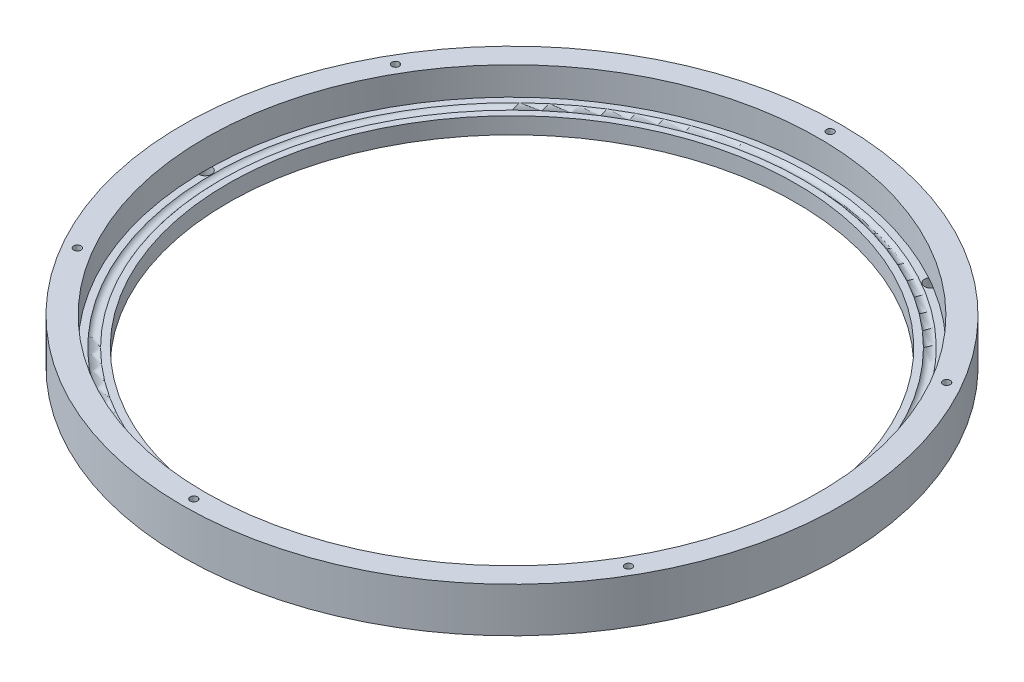
SolidWorks part; units mm, degrees
ref_plane "Front Plane" through (0, 0, 0) normal (0, 0, 1) x (1, 0, 0)
ref_plane "Top Plane" through (0, 0, 0) normal (0, 1, 0) x (1, 0, 0)
ref_plane "Right Plane" through (0, 0, 0) normal (1, 0, 0) x (0, 0, -1)
sketch "Sketch1" plane through (0, 0, 0) normal (0, 1, 0) x (1, 0, 0)
  line L0 (47.1487, -81.664) -> (0, 0) construction
  line L1 (0, 0) -> (0, -32.7983) construction
  circle A0 centre (0, 0) radius 87.3125
  circle A1 centre (0, 0) radius 101.2825
  circle A3 centre (0, 0) radius 94.2975
  circle A4 centre (0, -97.79) radius 1.1303
  circle A5 centre (47.1487, -81.664) radius 1.9939
  circle A6 centre (47.1487, -81.664) radius 5.588
  dimension "D1" = 174.625
  dimension "D5" = 2.2606
  dimension "D7" = 3.9878
  dimension "D9" = 11.176
  dimension "D4" = 97.79
  dimension "D6" = 94.2975
  dimension "D8" = 30
  dimension "D2" = 13.97
  dimension "D3" = 6.985
extrude "Boss-Extrude1" add sketch "Sketch1" along normal blind 5.08 contours A3 A0 | A1 A4 A3 | A3 A6 A5 | A3 A6 A5 region at (-98.4178, 0, 0) region at (80.6769, 0, 43.4438) region at (45.8339, 0, 79.3867) region at (48.4279, 0, 83.8795)
extrude "Boss-Extrude3" add sketch "Sketch1<3>" along normal blind 8.636 from surface contours A1 A4 A3 | A3 A5 | A3 A6 A5 region at (-98.4178, 0, 0) region at (48.4279, 0, 83.8795) region at (47.57, 0, 82.3936) starting at face at (47.1487, 5.08, 83.6579)
sketch "Sketch1<3>" plane through (0, 0, 0) normal (0, 1, 0) x (1, 0, 0) same geometry as "Sketch1"
pattern_circular "CirPattern1" count 6 over 360 about axis through (0, 13.716, 0) along (0, 1, 0) of face at (0, 0, 98.9203)
sketch "Sketch2" plane through (0, 0, 0) normal (1, 0, 0) x (0, 0, -1)
  line L0 (-87.3125, 0) -> (87.3125, 0) construction
  line L1 (87.3125, 5.08) -> (-87.3125, 5.08) construction
  line L2 (-87.3125, 0) -> (87.3125, 0)
  line L3 (87.3125, 5.08) -> (-87.3125, 5.08)
  line L4 (91.6697, 4.318) -> (97.1828, 4.318) construction
  line L5 (0, 5.08) -> (0, 35.8369)
  circle A0 centre (90.805, 5.9055) radius 1.5875 construction
  circle A1 centre (90.805, 5.969) radius 1.651
  dimension "D2" = 3.175
  dimension "D4" = 3.302
  dimension "D1" = 90.805
  dimension "D3" = 0.762
revolve "Cut-Revolve2" cut sketch "Sketch2" angle 360 about L5
extrude "Cut-Extrude2" cut sketch "Sketch1<4>" along normal blind 0.635 contours A3 A6 A5 | A3 A6 A5 region at (45.8339, 0, 79.3867) region at (48.4279, 0, 83.8795)
sketch "Sketch1<4>" plane through (0, 0, 0) normal (0, 1, 0) x (1, 0, 0) same geometry as "Sketch1"
pattern_circular "CirPattern3" count 3 over 360 about axis through (0, 0, 0) along (0, 1, 0) of face at (47.1487, 0.635, 83.6579) of face at (47.6472, 5.08, 82.5274) of face at (47.1487, 0.635, 83.6579) of face at (47.1487, 0.635, 87.252)
equation "\"Middle Coupler Inner Daimeter\"= 6.25in"
equation "\"Middle Coupler  Wall Thickness\" = 0.25in"
equation "\"Middle Coupler Bottom Thickness\"= 0.2in"
equation "\"Bearing Rail Offset\"= 0.45in"
equation "\"3-56 UNF Tap\"= 0.089in"
equation "\"3-56 UNF Clearance\"= 0.104in"
equation "\"Ball Bearing Distance\"= 0.03in"
equation "\"D1@Sketch1\"=\"Middle Coupler Inner Daimeter\"+0.625in"
equation "\"D3@Sketch1\"=\"D2@Sketch1\"/2"
equation "\"D4@Sketch1\"=(\"D1@Sketch1\"+\"D3@Sketch1\"+\"D2@Sketch1\")/2"
equation "\"D5@Sketch1\"=\"3-56 UNF Tap\""
equation "\"D1@Sketch2\"=\"Middle Coupler Inner Daimeter\"/2in + \"Bearing Rail Offset\""
equation "\"D3@Sketch2\"=\"Ball Bearing Distance\""
equation "\"D4@Sketch2\"=\"D2@Sketch2\"+0.005"
equation "\"D1@Boss-Extrude3\"=0.330in+0.01in"
equation "\"D6@Sketch1\"=(\"D1@Sketch1\"/2+\"D3@Sketch1\")"
equation "\"TCA Outer Diameter\" = 8.625in"
equation "\"Interstage Aeroframe Wall Thickness\" = 0.072in"
equation "\"Compression Spring OD\"= 0.42in"
equation "\"10-24 Tap\"= 0.157in"
equation "\"10-24 Clearance\"= 0.196in"
